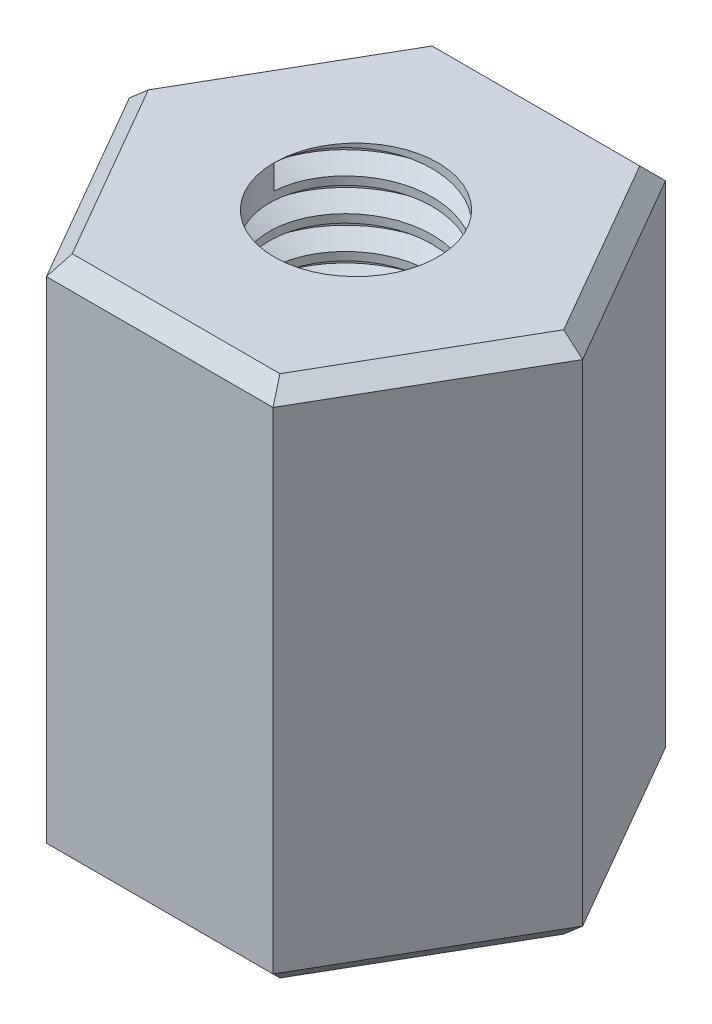
SolidWorks part; units mm, degrees
ref_plane "Front Plane" through (0, 0, 0) normal (0, 0, 1) x (1, 0, 0)
ref_plane "Top Plane" through (0, 0, 0) normal (0, 1, 0) x (1, 0, 0)
ref_plane "Right Plane" through (0, 0, 0) normal (1, 0, 0) x (0, 0, -1)
sketch "Sketch2" plane through (0, 0, 0) normal (0, 1, 0) x (1, 0, 0)
  line L1 (3.4641, 0) -> (1.7321, 3)
  line L2 (1.7321, 3) -> (-1.7321, 3)
  line L3 (-1.7321, 3) -> (-3.4641, 0)
  line L4 (-3.4641, 0) -> (-1.7321, -3)
  line L5 (-1.7321, -3) -> (1.7321, -3)
  line L6 (1.7321, -3) -> (3.4641, 0)
  circle A0 centre (0, 0) radius 3 construction
  circle A1 centre (0, 0) radius 1.25
extrude "Boss-Extrude1" add sketch "Sketch2" along normal blind 8
thread "Thread1" pitch 0.5 method cut profile "Thread Profile1" start angle 0, offset 0, length 0, pitch 0.5, diameter 2.5
ref_plane "Plane1" through (-1.25, 8, 0) normal (0, 0, 1) x (-1, 0, 0)
sketch "Thread Profile1" plane through (-1.25, 8, 0) normal (0, 0, 1) x (-1, 0, 0)
  line L0 (0, 0) -> (0, 0.5) construction
  line L1 (0, 0) -> (0.2706, 0.1562)
  line L2 (0.2706, 0.1562) -> (0.2706, 0.2187)
  line L3 (0.2706, 0.2187) -> (0, 0.375)
  line L4 (0.2706, 0.1875) -> (0, 0.1875) construction
  line L11 (0, 0) -> (0, 0.375)
  point P2 (0, 0)
  dimension "Pitch" = 0.5
  dimension "Profile_Angle" = 60
  dimension "Profile_Land" = 0.0625
  dimension "Profile_Height" = 0.2706
chamfer "Chamfer2" distance 0.25 angle 45 12 edges at (-2.5981, 0, -1.5) (0, 0, -3) (2.5981, 0, -1.5) (2.5981, 0, 1.5) (0, 0, 3) (-2.5981, 0, 1.5) (-2.5981, 8, -1.5) (0, 8, -3) (2.5981, 8, -1.5) (2.5981, 8, 1.5) (-2.5981, 8, 1.5) (0, 8, 3)
